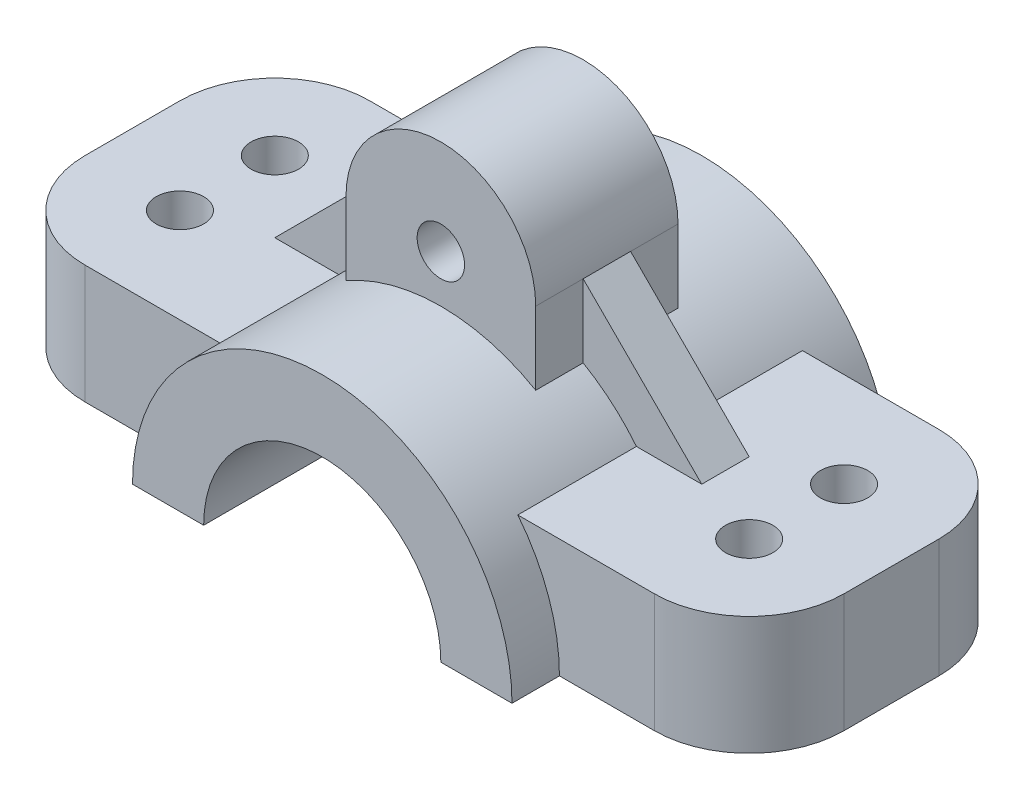
SolidWorks part; units mm, degrees
ref_plane "Płaszczyzna przednia" through (0, 0, 0) normal (0, 0, 1) x (1, 0, 0)
ref_plane "Płaszczyzna górna" through (0, 0, 0) normal (0, 1, 0) x (1, 0, 0)
ref_plane "Płaszczyzna prawa" through (0, 0, 0) normal (1, 0, 0) x (0, 0, -1)
sketch "Sketch1" plane through (0, 0, 0) normal (0, 0, 1) x (1, 0, 0)
  line L0 (-80, 0) -> (80, 0)
  line L1 (80, 0) -> (80, 25)
  line L2 (80, 25) -> (31.225, 25)
  line L3 (0, 50) -> (0, 0) construction
  line L4 (20, 50) -> (20, 34.641)
  line L5 (0, 50) -> (0, 85.179) construction
  line L6 (-20, 50) -> (-20, 34.641)
  line L7 (-80, 25) -> (-31.225, 25)
  line L8 (-80, 0) -> (-80, 25)
  line L9 (-20, 50) -> (-45, 25)
  line L10 (20, 50) -> (45, 25)
  arc A0 (40, 0) -> (-40, 0) centre (0, 0) ccw
  arc A1 (25, 0) -> (-25, 0) centre (0, 0) ccw
  arc A2 (20, 50) -> (-20, 50) centre (0, 50) ccw
  circle A3 centre (0, 50) radius 5
  point P3 (0, 0)
  dimension "D3" = 80
  dimension "D4" = 50
  dimension "D5" = 40
  dimension "D7" = 10
  dimension "D1" = 160
  dimension "D2" = 25
  dimension "D6" = 50
  dimension "D8" = 90
extrude "Boss-Extrude1" add sketch "Sketch1" along normal mid plane 80 contours A1 L0 A0 region at (-36.8986, 12.9514, 0)
extrude "Boss-Extrude2" add sketch "Sketch1<3>" along normal mid plane 60 contours A0 L0 L1 L2 | A0 L7 L8 L0 region at (-58.5314, 12.9161, 0) region at (58.5314, 12.9161, 0)
sketch "Sketch1<3>" plane through (0, 0, 0) normal (0, 0, 1) x (1, 0, 0) same geometry as "Sketch1"
extrude "Boss-Extrude3" add sketch "Sketch1<5>" along normal mid plane 10 contours A0 L2 L10 L4 | A0 L6 L9 L7 region at (-29.3898, 34.5241, 0) region at (29.3898, 34.5241, 0)
sketch "Sketch1<5>" plane through (0, 0, 0) normal (0, 0, 1) x (1, 0, 0) same geometry as "Sketch1"
extrude "Boss-Extrude4" add sketch "Sketch1<6>" along normal mid plane 30 contours L4 A2 L6 A0 A3 region at (-19.4661, 42.3205, 0)
sketch "Sketch1<6>" plane through (0, 0, 0) normal (0, 0, 1) x (1, 0, 0) same geometry as "Sketch1"
sketch "Sketch3" plane through (0, 25, 0) normal (0, 1, 0) x (1, 0, 0)
  line L0 (-80, 0) -> (80, 0) construction
  line L1 (-80, -30) -> (-80, 30) construction
  line L2 (80, -30) -> (80, 30) construction
  line L3 (0, 40) -> (0, -40) construction
  line L4 (40, 40) -> (-40, 40) construction
  line L5 (-40, -40) -> (40, -40) construction
  point P0 (-60, 10)
  point P13 (-60, -10)
  point P14 (0, 0)
  point P15 (60, -10)
  point P16 (60, 10)
  dimension "D1" = 120
  dimension "D2" = 20
hole_wizard "Ø10.0 (10) Diameter Hole1" positions "3DSketch2" profile "Sketch4" hole size "Ø10.0" standard "ISO" end condition through all
sketch3d "3DSketch2"
  point P0 (-60, 25, -10)
  point P3 (-60, 25, 10)
  point P6 (60, 25, 10)
  point P9 (60, 25, -10)
sketch "Sketch4" plane through (-60, 25, -10) normal (1, 0, 0) x (0, 0, 1)
  line L0 (0, 0) -> (0, 25)
  line L1 (0, 25) -> (5, 25)
  line L2 (5, 25) -> (5, 0)
  line L5 (5, 0) -> (0, 0)
  line L11 (0, -6.35) -> (0, 107.95) construction
  dimension "Thru Hole Dia." = 10
  dimension "Thru Hole Depth" = 25
fillet "Fillet2" radius 20 4 edges at (80, 12.5, -30) (80, 12.5, 30) (-80, 12.5, 30) (-80, 12.5, -30)
